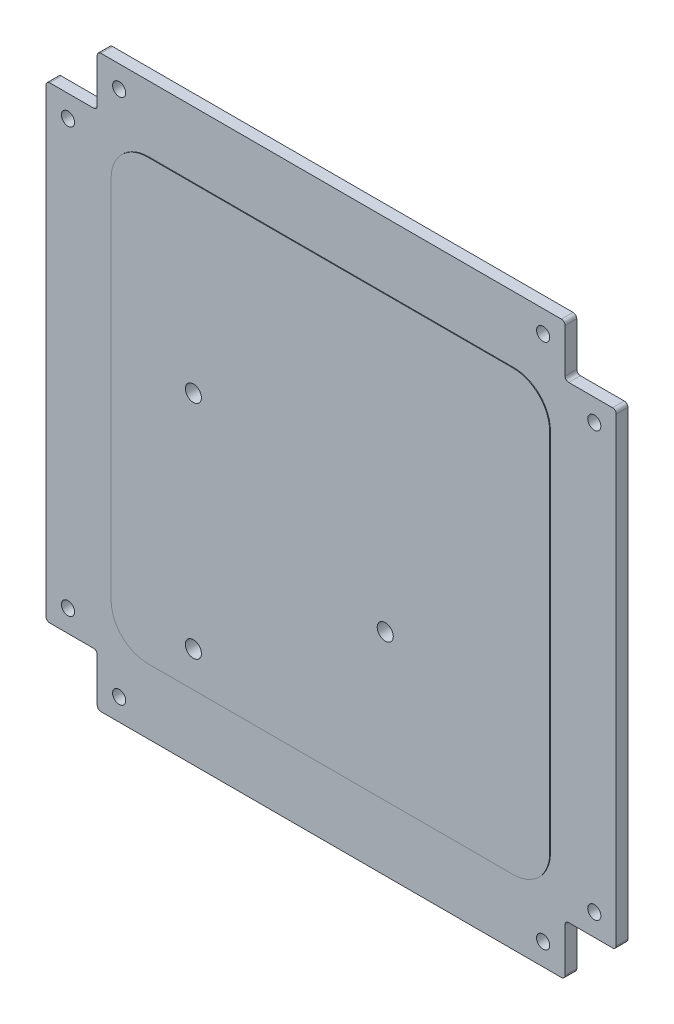
SolidWorks part; units mm, degrees
material "PET"
ref_plane "Front Plane" through (0, 0, 0) normal (0, 0, 1) x (1, 0, 0)
ref_plane "Top Plane" through (0, 0, 0) normal (0, 1, 0) x (1, 0, 0)
ref_plane "Right Plane" through (0, 0, 0) normal (1, 0, 0) x (0, 0, -1)
sketch "Sketch1" plane through (0, 0, 0) normal (0, 0, 1) x (1, 0, 0)
  line L0 (-32, 38.5) -> (-32, 32.5)
  line L1 (-31.5, -39) -> (31.5, -39)
  line L2 (-39, 31.5) -> (-39, -31.5)
  line L3 (-31.5, 39) -> (31.5, 39)
  line L4 (39, -31.5) -> (39, 31.5)
  line L5 (32, -38.5) -> (32, -32.5)
  line L6 (32.5, -32) -> (38.5, -32)
  line L7 (-32.5, 32) -> (-38.5, 32)
  line L8 (32, 38.5) -> (32, 32.5)
  line L9 (32.5, 32) -> (38.5, 32)
  line L10 (-38.5, -32) -> (-32.5, -32)
  line L11 (-32, -32.5) -> (-32, -38.5)
  line L12 (-32.5, -32.5) -> (32.5, 32.5) construction
  line L13 (32.5, -32.5) -> (-32.5, 32.5) construction
  arc A0 (-31.5, 39) -> (-32, 38.5) centre (-31.5, 38.5) ccw
  arc A1 (31.5, 39) -> (32, 38.5) centre (31.5, 38.5) cw
  arc A2 (32, 32.5) -> (32.5, 32) centre (32.5, 32.5) ccw
  arc A3 (38.5, 32) -> (39, 31.5) centre (38.5, 31.5) cw
  arc A4 (31.5, -39) -> (32, -38.5) centre (31.5, -38.5) ccw
  arc A5 (32.5, -32) -> (32, -32.5) centre (32.5, -32.5) ccw
  arc A6 (38.5, -32) -> (39, -31.5) centre (38.5, -31.5) ccw
  arc A7 (-32, -38.5) -> (-31.5, -39) centre (-31.5, -38.5) ccw
  arc A8 (-32, -32.5) -> (-32.5, -32) centre (-32.5, -32.5) ccw
  arc A9 (-39, -31.5) -> (-38.5, -32) centre (-38.5, -31.5) ccw
  arc A10 (-38.5, 32) -> (-39, 31.5) centre (-38.5, 31.5) ccw
  arc A11 (-32.5, 32) -> (-32, 32.5) centre (-32.5, 32.5) ccw
  point P0 (0, 0)
  dimension "D4" = 0.5
  dimension "D1" = 7
  dimension "D2" = 7
  dimension "D3" = 7
  dimension "D5" = 7
  dimension "D6" = 7
  dimension "D7" = 7
  dimension "D8" = 7
  dimension "D9" = 7
  dimension "D10" = 78
  dimension "D11" = 78
extrude "Boss-Extrude1" add sketch "Sketch1" along normal blind 1.6
sketch "Esboço1" plane through (0, 0, 1.6) normal (0, 0, 1) x (1, 0, 0)
  line L1 (-25, -30) -> (25, -30)
  line L2 (-30, -25) -> (-30, 25)
  line L3 (-25, 30) -> (25, 30)
  line L4 (30, -25) -> (30, 25)
  line L5 (-25, -25) -> (25, 25) construction
  line L6 (-25, 25) -> (25, -25) construction
  arc A0 (-30, 25) -> (-25, 30) centre (-25, 25) cw
  arc A1 (25, 30) -> (30, 25) centre (25, 25) cw
  arc A2 (30, -25) -> (25, -30) centre (25, -25) cw
  arc A3 (-25, -30) -> (-30, -25) centre (-25, -25) cw
  point P0 (0, 0)
  dimension "D1" = 5
  dimension "D2" = 60
  dimension "D3" = 60
extrude "Boss-Extrude2" add sketch "Esboço1" along normal blind 0.1
hole_wizard "M1.6 Hole1-FixingStructure" positions "Sketch3" profile "Sketch2" hole size "M1.6" standard "DIN"
sketch "Sketch3" plane through (0, 0, 0) normal (0, 0, -1) x (-1, 0, 0)
  line L0 (-31.5, 39) -> (31.5, 39) construction
  line L1 (31.5, -39) -> (-31.5, -39) construction
  line L2 (-39, -31.5) -> (-39, 31.5) construction
  line L3 (39, 31.5) -> (39, -31.5) construction
  line L4 (-31.5, 39) -> (31.5, 39) construction
  line L5 (31.5, -39) -> (-31.5, -39) construction
  line L6 (39, 31.5) -> (39, -31.5) construction
  line L7 (-39, -31.5) -> (-39, 31.5) construction
  point P0 (-29, 36)
  point P2 (29, 36)
  point P4 (-29, -36)
  point P6 (29, -36)
  point P20 (36, 29)
  point P22 (36, -29)
  point P24 (-36, -29)
  point P26 (-36, 29)
  dimension "D1" = 3
  dimension "D2" = 3
  dimension "D3" = 10
  dimension "D4" = 10
  dimension "D5" = 10
  dimension "D6" = 10
  dimension "D7" = 3
  dimension "D8" = 3
sketch "Sketch2" plane through (29, 36, 0) normal (1, 0, 0) x (0, 1, 0)
  line L0 (0, 0) -> (0, 200.5408)
  line L1 (0, 200.5408) -> (0.9, 200)
  line L2 (0.9, 200) -> (0.9, 0)
  line L5 (0.9, 0) -> (0, 0)
  line L10 (0, 200.5408) -> (-0.9, 200) construction
  line L11 (0, -6.35) -> (0, 107.95) construction
  dimension "Hole Dia." = 1.8
  dimension "Hole Depth" = 200
  dimension "Drill Angle" = 118
sketch "Sketch4" plane through (0, 0, 1.7) normal (0, 0, 1) x (1, 0, 0)
  circle A0 centre (-18.75, 5.1554) radius 1.1 construction
  circle A1 centre (-18.75, -25.1554) radius 1.1 construction
  circle A2 centre (7.5, -10) radius 1.1 construction
  circle A3 centre (-18.75, 5.1554) radius 1.1
  circle A4 centre (-18.75, -25.1554) radius 1.1
  circle A5 centre (7.5, -10) radius 1.1
extrude "Cut-Extrude1" cut sketch "Sketch4" against normal up to surface (1.7 mm away) up to face at (28.1, 36, 0)
